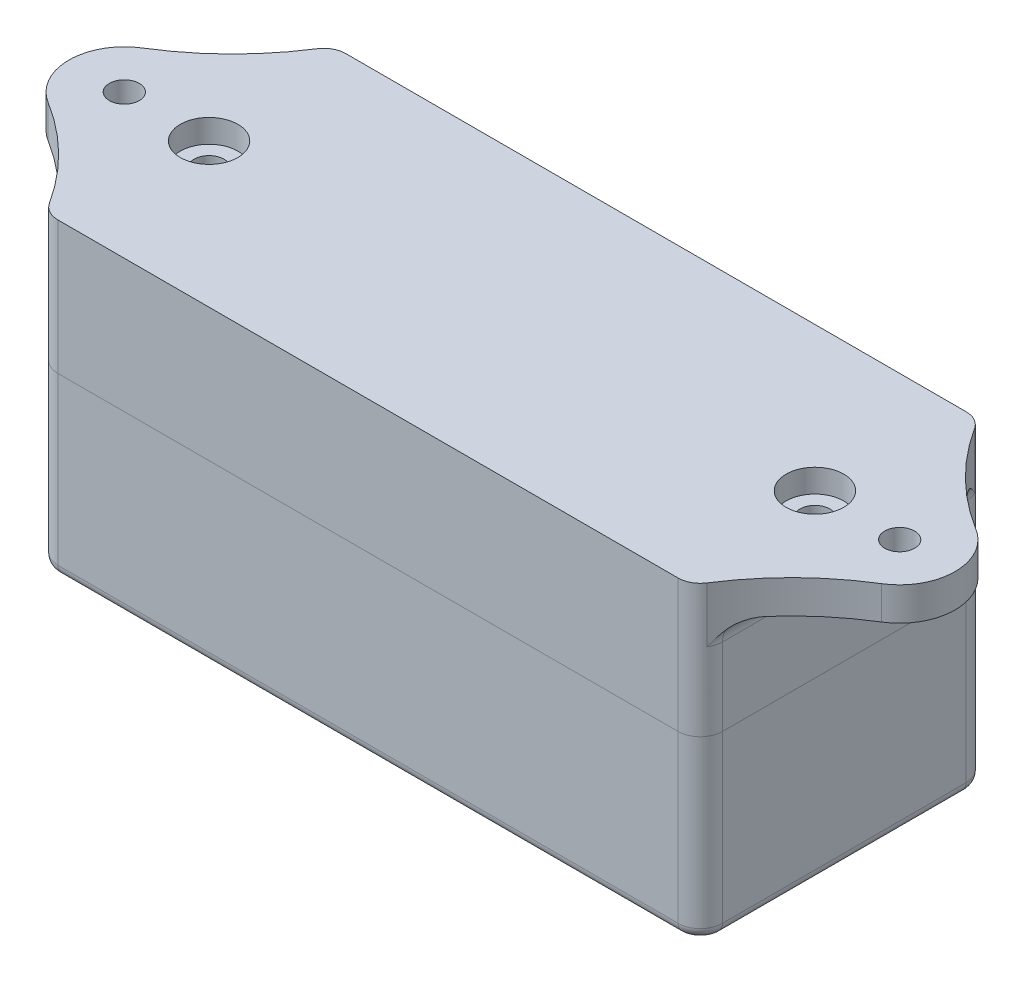
SolidWorks part; units mm, degrees
other "Top Cover"
other "Base Holder"
ref_plane "Front Plane" through (0, 0, 0) normal (0, 0, 1) x (1, 0, 0)
ref_plane "Top Plane" through (0, 0, 0) normal (0, 1, 0) x (1, 0, 0)
ref_plane "Right Plane" through (0, 0, 0) normal (1, 0, 0) x (0, 0, -1)
sketch "Sketch1" plane through (0, 0, 0) normal (0, 1, 0) x (1, 0, 0)
  line L1 (-30, 13) -> (30, 13)
  line L2 (-30, 13) -> (-30, -13)
  line L3 (-30, -13) -> (30, -13)
  line L4 (30, 13) -> (30, -13)
  line L5 (-30, 13) -> (30, -13) construction
  line L6 (-30, -13) -> (30, 13) construction
  point P0 (0, 0)
  dimension "D1" = 26
  dimension "D2" = 60
extrude "Boss-Extrude1" add sketch "Sketch1" along normal blind 16
shell "Shell1" thickness 2 removed face at (0, 16, 0)
sketch "Sketch2" plane through (0, 2, 0) normal (0, 1, 0) x (1, 0, 0)
  line L0 (-25.7, 11) -> (-25.7, -11)
  line L1 (-24.7, 11) -> (-24.7, -11)
  line L2 (-20.1, 11) -> (-20.1, -11)
  line L3 (-19.1, 11) -> (-19.1, -11)
  line L4 (28, -11) -> (28, 11)
  line L5 (28, 11) -> (-28, 11)
  line L6 (-28, 11) -> (-28, -11)
  line L7 (-28, -11) -> (28, -11)
  line L8 (28, -11) -> (28, 11)
  line L9 (-19.1, 11) -> (-20.1, 11)
  line L10 (-28, 11) -> (-28, -11) construction
  line L11 (-25.7, -11) -> (-24.7, -11)
  line L12 (-24.7, 11) -> (-25.7, 11)
  line L13 (-20.1, -11) -> (-19.1, -11)
  line M10 (28, 11) -> (-28, 11)
  line M12 (-28, -11) -> (28, -11)
  dimension "D2" = 1
  dimension "D3" = 1
  dimension "D4" = 4.6
  dimension "D5" = 2.3
  dimension "D1" = 0
extrude "Boss-Extrude2" add sketch "Sketch2" along normal up to surface (14 mm away) contours L1 L0 M10 M12 | L3 L2 M10 M12 region at (-25.2, 2, 0) region at (-19.6, 2, 0) up to face at (0, 16, 0)
pattern_linear "LPattern1" count 9 spacing 5.6 along (1, 0, 0) of "Boss-Extrude2"
sketch "Sketch3" plane through (-28, 0, 0) normal (1, 0, 0) x (0, 0, -1)
  line L4 (-11, 2) -> (11, 2)
  line L5 (11, 2) -> (11, 16)
  line L6 (11, 16) -> (-11, 16)
  line L7 (-11, 16) -> (-11, 2)
  line L8 (-11, 2) -> (11, 2)
  line L9 (11, 2) -> (11, 13)
  line L11 (-11, 13) -> (-11, 2)
  arc A0 (-11, 13) -> (11, 13) centre (0, 13) ccw
  line M6 (-11, 2) -> (11, 2)
  line M7 (11, 2) -> (11, 16)
  line M9 (-11, 16) -> (-11, 2)
  dimension "D1" = 0
extrude "Boss-Extrude3" add sketch "Sketch3" along normal up to surface (52.7 mm away) from surface contours A0 L8 M7 | A0 M9 M6 region at (-28, 4.457, 8.543) region at (-28, 4.457, -8.543) up to face at (24.7, 9, 0) starting at face at (-24.7, 9, 0)
sketch "Sketch4" plane through (-28, 0, 0) normal (1, 0, 0) x (0, 0, -1)
  line L0 (-1.025, 0) -> (-1.025, 12.575)
  line L1 (13, 0) -> (-13, 0) construction
  line L2 (1.025, 12.575) -> (1.025, 0)
  line L3 (1.025, 0) -> (-1.025, 0)
  arc A0 (-1.025, 12.575) -> (1.025, 12.575) centre (0, 12.575) cw
  arc A2 (-11, 13) -> (11, 13) centre (0, 13) ccw construction
  point P6 (0, 0)
  point P8 (0, 2)
  point P10 (0, 13.6)
  dimension "D2" = 11.6
  dimension "D1" = 2.05
extrude "Boss-Extrude4" add sketch "Sketch4" along normal up to surface (52.7 mm away) from surface up to face at (24.7, 11.75, 0) starting at face at (-24.7, 11.75, 0)
sketch "Sketch6" plane through (0, 2, 0) normal (0, 1, 0) x (1, 0, 0)
  line L0 (25.7, 11) -> (25.7, -11) construction
  line L1 (25.7, -11) -> (28, -11) construction
  line L2 (28, -11) -> (28, 11) construction
  line L3 (28, 11) -> (25.7, 11) construction
  line L4 (-28, -11) -> (-25.7, -11) construction
  line L5 (-25.7, -11) -> (-25.7, 11) construction
  line L6 (-25.7, 11) -> (-28, 11) construction
  line L7 (-28, 11) -> (-28, -11) construction
  line L8 (25.7, 11) -> (25.7, -11)
  line L9 (25.7, -11) -> (28, -11)
  line L10 (28, -11) -> (28, 11)
  line L11 (28, 11) -> (25.7, 11)
  line L12 (-28, -11) -> (-25.7, -11)
  line L13 (-25.7, -11) -> (-25.7, 11)
  line L14 (-25.7, 11) -> (-28, 11)
  line L15 (-28, 11) -> (-28, -11)
extrude "Boss-Extrude5" add sketch "Sketch6" along normal up to surface (14 mm away) up to face at (22.4, 16, 0)
sketch "Sketch12" plane through (0, 16, 0) normal (0, 1, 0) x (1, 0, 0)
  line L0 (24.7, 0) -> (30, 0) construction
  line L2 (24.7, 11) -> (24.7, -11) construction
  line L3 (30, -13) -> (30, 13) construction
  line L4 (-24.7, 0) -> (-30, 0) construction
  line L5 (-24.7, 11) -> (-24.7, -11) construction
  line L6 (-30, 13) -> (-30, -13) construction
  circle A0 centre (27.35, 0) radius 1.675
  circle A1 centre (-27.35, 0) radius 1.675
  point P9 (-27.35, 0)
  point P10 (27.35, 0)
  dimension "D1" = 3.35
extrude "Cut-Extrude2" cut sketch "Sketch12" against normal blind 8
sketch "Sketch8" plane through (0, 16, 0) normal (0, 1, 0) x (1, 0, 0)
  line L4 (30, -13) -> (30, 13)
  line L5 (30, 13) -> (-30, 13)
  line L6 (-30, 13) -> (-30, -13)
  line L7 (-30, -13) -> (30, -13)
  line L8 (30, -13) -> (30, 13)
  line L9 (30, 13) -> (-30, 13)
  line L10 (-30, 13) -> (-30, -13)
  line L11 (-30, -13) -> (30, -13)
  dimension "D1" = 0
extrude "Boss-Extrude6" add sketch "Sketch8" along normal blind 12 separate body
sketch "Sketch10" plane through (0, 16, 0) normal (0, 1, 0) x (1, 0, 0)
  line L0 (-24.7, 11) -> (-24.7, -11)
  line L1 (-24.7, -11) -> (24.7, -11)
  line L2 (24.7, -11) -> (24.7, 11)
  line L3 (24.7, 11) -> (-24.7, 11)
extrude "Cut-Extrude1" cut sketch "Sketch10" along normal blind 10
sketch "Sketch13" plane through (0, 28, 0) normal (0, 1, 0) x (1, 0, 0)
  circle A0 centre (-27.35, 0) radius 1.675 construction
  circle A1 centre (27.35, 0) radius 1.675 construction
  circle A2 centre (-27.35, 0) radius 1.675 construction
  circle A3 centre (27.35, 0) radius 1.675 construction
  circle A4 centre (-27.35, 0) radius 1.35
  circle A5 centre (27.35, 0) radius 1.35
  dimension "D1" = 2.7
extrude "Cut-Extrude3" cut sketch "Sketch13" against normal up to next (12 mm away)
sketch "Sketch14" plane through (0, 28, 0) normal (0, 1, 0) x (1, 0, 0)
  circle A0 centre (-27.35, 0) radius 2.6
  circle A1 centre (27.35, 0) radius 2.6
  dimension "D1" = 5.2
extrude "Cut-Extrude4" cut sketch "Sketch14" against normal blind 2.1
sketch "Sketch15" plane through (0, 28, 0) normal (0, 1, 0) x (1, 0, 0)
  line L0 (-30, 5) -> (-35, 5)
  line L1 (-30, 13) -> (-30, -13) construction
  line L2 (-35, -5) -> (-30, -5)
  arc A0 (-35, 5) -> (-35, -5) centre (-35, 0) ccw
  circle A1 centre (-35, 0) radius 1.35
  point P6 (-30, 0)
  line M11 (-30, 13) -> (-30, -13)
  dimension "D2" = 5
  dimension "D3" = 2.7
  dimension "D1" = 10
extrude "Boss-Extrude7" add sketch "Sketch15" against normal blind 3 contours L0 A0 L2 A1 M11 region at (-30.1414, 28, 0)
mirror "Mirror1" about plane through (0, 0, 0) normal (1, 0, 0) of "Boss-Extrude7"
fillet "Fillet1" radius 2 4 edges at (-30, 8, -13) (30, 8, -13) (30, 8, 13) (-30, 8, 13)
fillet "Fillet2" radius 2 4 edges at (30, 22, 13) (30, 22, -13) (-30, 22, -13) (-30, 22, 13)
fillet "Fillet6" radius 1 8 edges at (-29.4142, 0, 12.4142) (-30, 0, 0) (-29.4142, 0, -12.4142) (0, 0, -13) (29.4142, 0, -12.4142) (30, 0, 0) (29.4142, 0, 12.4142) (0, 0, 13)
fillet "Fillet9" radius 25 4 edges at (30, 26.5, 5) (30, 26.5, -5) (-30, 26.5, -5) (-30, 26.5, 5)
fillet "Fillet10" radius 2 6 edges at (29.9198, 25, -11.5605) (29.9198, 25, 11.5605) (-29.9198, 25, -11.5605) (-29.9198, 25, 11.5605) (30, 25, 0) (-30, 25, 0)
